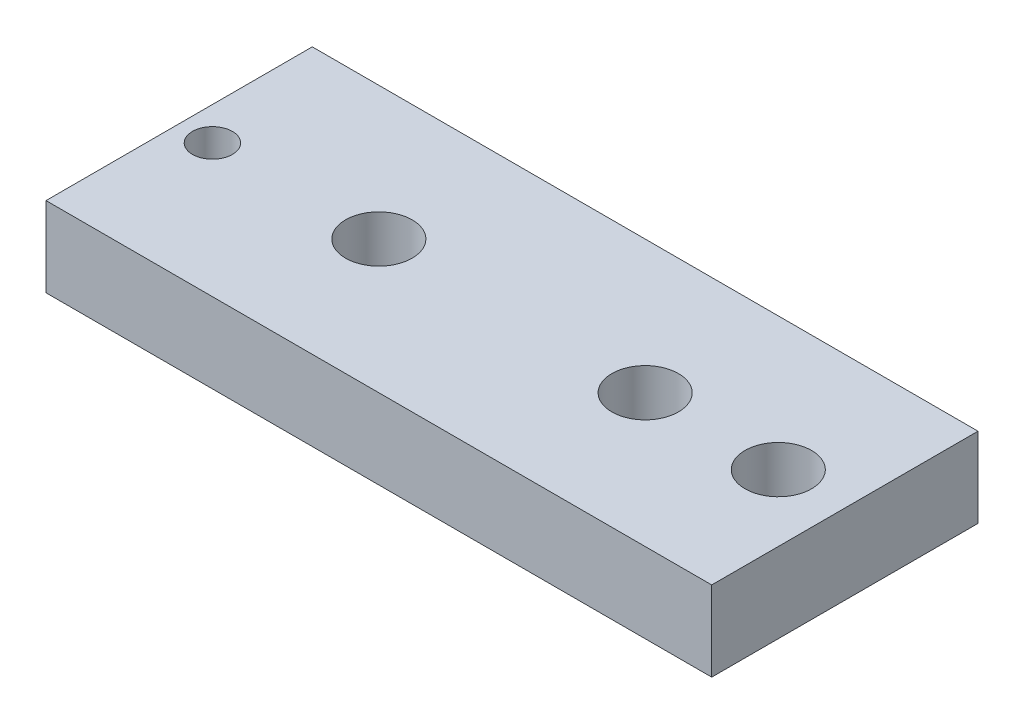
SolidWorks part; units mm, degrees
ref_plane "Front Plane" through (0, 0, 0) normal (0, 0, 1) x (1, 0, 0)
ref_plane "Top Plane" through (0, 0, 0) normal (0, 1, 0) x (1, 0, 0)
ref_plane "Right Plane" through (0, 0, 0) normal (1, 0, 0) x (0, 0, -1)
sketch "Sketch1" plane through (0, 0, 0) normal (0, 1, 0) x (1, 0, 0)
  line L0 (0, 0) -> (10, 0) construction
  line L1 (-25, -10) -> (25, -10)
  line L2 (-25, -10) -> (-25, 10)
  line L3 (-25, 10) -> (25, 10)
  line L4 (25, -10) -> (25, 10)
  line L5 (-25, -10) -> (25, 10) construction
  line L6 (-25, 10) -> (25, -10) construction
  line L7 (0, 0) -> (-10, 0) construction
  circle A0 centre (20, 0) radius 2.5
  circle A1 centre (-10, 0) radius 2.5
  circle A2 centre (10, 0) radius 2.5
  circle A3 centre (-22.5, 0) radius 1.5
  point P0 (0, 0)
  dimension "D2" = 5
  dimension "D5" = 5
  dimension "D6" = 5
  dimension "D8" = 3
  dimension "D1" = 20
  dimension "D3" = 5
  dimension "D4" = 20
  dimension "D7" = 50
  dimension "D9" = 2.5
extrude "Boss-Extrude1" add sketch "Sketch1" along normal blind 6 contours L3 L4 L1 L2
extrude "Cut-Extrude1" cut sketch "Sketch1<3>" along normal blind 6 contours A3 | A1 | A2 | A0
sketch "Sketch1<3>" plane through (0, 0, 0) normal (0, 1, 0) x (1, 0, 0) same geometry as "Sketch1"
